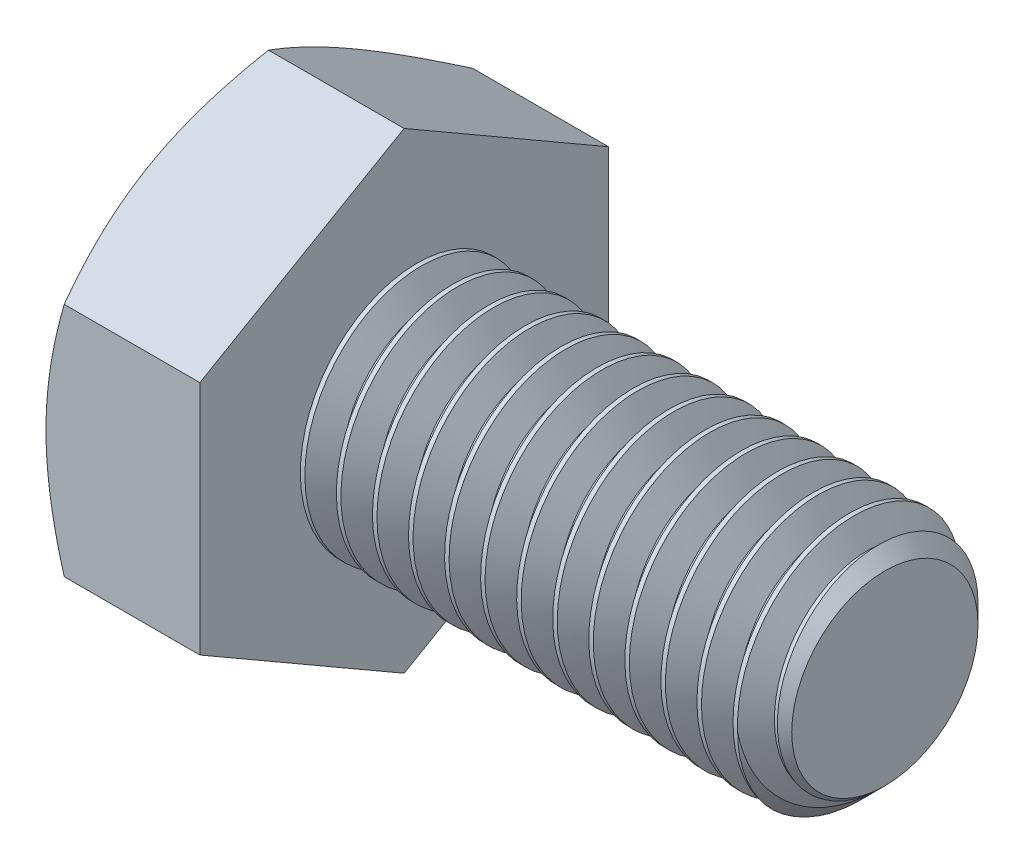
SolidWorks part; units mm, degrees
ref_plane "Front Plane" through (0, 0, 0) normal (0, 0, 1) x (1, 0, 0)
ref_plane "Top Plane" through (0, 0, 0) normal (0, 1, 0) x (1, 0, 0)
ref_plane "Right Plane" through (0, 0, 0) normal (1, 0, 0) x (0, 0, -1)
sketch "Sketch1" plane through (0, 0, 0) normal (0, 0, 1) x (1, 0, 0)
  line L0 (-13.2, 0) -> (13.2, 0) construction
  line L1 (-6.8, 8.5) -> (-6.8, -8.5) construction
  line L2 (-13.2, 8.5) -> (-13.2, -8.5) construction
  line L3 (13.2, 5) -> (13.2, -5) construction
  point P8 (7.95, -5)
  dimension "Thread Dia" = 10
  dimension "Hex" = 17
  dimension "Head Ht" = 6.4
  dimension "Length" = 20
  dimension "D1" = 5.25
ref_plane "Plane2" through (13.2, 0, 0) normal (1, 0, 0) x (0, 0, -1)
sketch "Sketch2" plane through (13.2, 0, 0) normal (1, 0, 0) x (0, 0, -1)
  circle A0 centre (0, 0) radius 5
extrude "Boss-Extrude1" add sketch "Sketch2" against normal up to vertex (20 mm away) up to point (-6.8, -8.5, 0)
sketch "Sketch4" plane through (13.2, 0, 0) normal (1, 0, 0) x (0, 0, -1)
  circle A1 centre (0, 0) radius 5
  circle A2 centre (0, 0) radius 5
  dimension "D1" = 0
curve "Helix/Spiral1" pitch 1.5 height 21.5 turns 14.3333 parameters "Pitch"=1.5
chamfer "Chamfer1" distance 1.125 angle 45 1 edges at (13.2, 0, -5)
sketch "Sketch5" plane through (0, 0, 0) normal (0, 0, 1) x (1, 0, 0)
  line L0 (13.2, 5) -> (13.7625, 4.0257)
  line L1 (13.7625, 4.0257) -> (13.95, 4.0257)
  line L2 (13.95, 4.0257) -> (14.5125, 5)
  line L3 (13.2, 5) -> (14.5125, 5)
  line L4 (13.8562, 4.0257) -> (13.8562, 5) construction
  line L5 (13.4812, 4.5129) -> (14.2313, 4.5129) construction
  line L6 (13.2, -5) -> (13.2, 5) construction
  dimension "D1" = 60
  dimension "D2" = 0.1875
  dimension "D3" = 0.75
sweep "Cut-Sweep1" cut profiles "Sketch5" path "Helix/Spiral1" align with end faces yes
sketch "Sketch3" plane through (-6.8, 0, 0) normal (-1, 0, 0) x (0, 0, 1)
  line L0 (0, 8.5) -> (0, -8.5) construction
  line L1 (-8.5, -4.9075) -> (0, -9.815)
  line L2 (0, -9.815) -> (8.5, -4.9075)
  line L3 (8.5, -4.9075) -> (8.5, 4.9075)
  line L4 (8.5, 4.9075) -> (0, 9.815)
  line L5 (0, 9.815) -> (-8.5, 4.9075)
  line L6 (-8.5, 4.9075) -> (-8.5, -4.9075)
  circle A0 centre (0, 0) radius 8.5 construction
extrude "Boss-Extrude2" add sketch "Sketch3" along normal up to vertex (6.4 mm away) up to point (-13.2, -8.5, 0)
sketch "Sketch6" plane through (-13.2, 0, 0) normal (-1, 0, 0) x (0, 0, 1)
  circle A0 centre (0, 0) radius 8.5 construction
  circle A1 centre (0, 0) radius 8.5
extrude "Cut-Extrude1" cut sketch "Sketch6" against normal through all draft 60 flip side to cut
sketch "Sketch9" plane through (0, 0, 0) normal (0, 0, 1) x (1, 0, 0)
  line L0 (-6.8, 5) -> (-6.8, 0)
  line L1 (-6.8, 0) -> (-35.8, 0)
  line L2 (-35.8, 0) -> (-40.8, 5)
  line L3 (-40.8, 5) -> (-6.8, 5)
  line L4 (-13.2, 0) -> (13.2, 0) construction
  line L5 (-6.8, 8.5) -> (-6.8, -8.5) construction
  line L6 (13.2, 5) -> (13.2, -5) construction
  dimension "D1" = 45
  dimension "MinThreadLg" = 54
revolve "Revolve1" [suppressed] add sketch "Sketch9" angle 360 about L1
equation "\"D2@Sketch5\" = \"Pitch@Helix/Spiral1\"*.125"
equation "\"D3@Sketch5\" = \"Pitch@Helix/Spiral1\"*.50"
equation "\"D3@Helix/Spiral1\" = \"Length@Sketch1\"+\"Pitch@Helix/Spiral1\""
equation "\"D1@Chamfer1\" = \"Pitch@Helix/Spiral1\"*.750"
equation "\"D1@Sketch1\" = \"Pitch@Helix/Spiral1\"*3.50"
